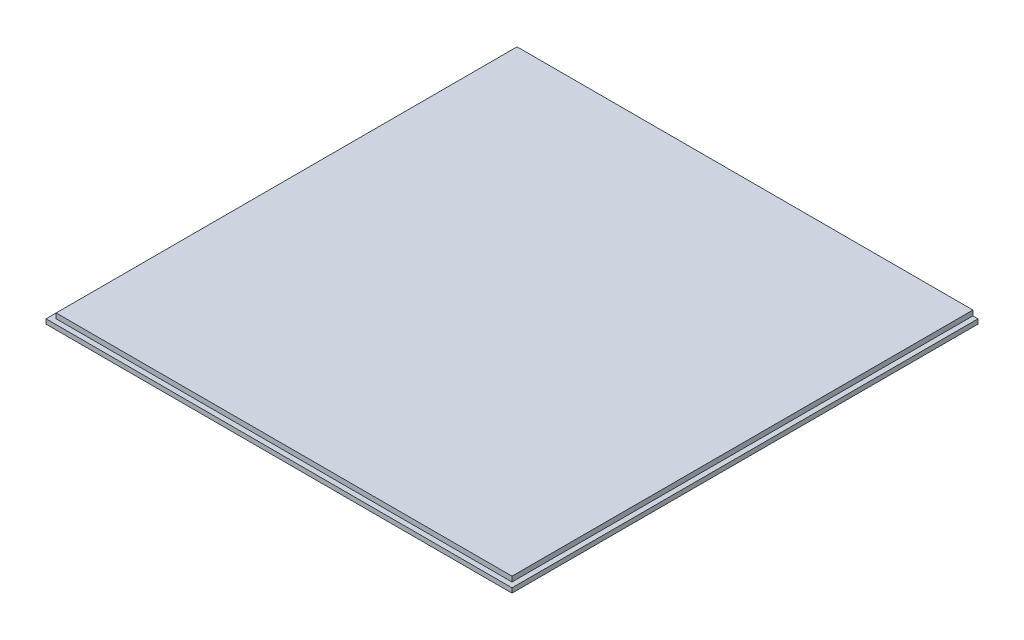
SolidWorks part; units mm, degrees
ref_plane "Front Plane" through (0, 0, 0) normal (0, 0, 1) x (1, 0, 0)
ref_plane "Top Plane" through (0, 0, 0) normal (0, 1, 0) x (1, 0, 0)
ref_plane "Right Plane" through (0, 0, 0) normal (1, 0, 0) x (0, 0, -1)
sketch "Sketch1" plane through (0, 0, 0) normal (0, 1, 0) x (1, 0, 0)
  line L1 (-438.9437, -438.9437) -> (438.9438, -438.9437)
  line L2 (-438.9437, -438.9437) -> (-438.9437, 438.9438)
  line L3 (-438.9437, 438.9438) -> (438.9438, 438.9438)
  line L4 (438.9438, -438.9437) -> (438.9438, 438.9438)
  line L5 (-438.9437, -438.9437) -> (438.9438, 438.9438) construction
  line L6 (-438.9437, 438.9438) -> (438.9438, -438.9437) construction
  point P0 (0, 0)
  dimension "D1" = 877.8875
  dimension "D2" = 877.8875
extrude "Boss-Extrude1" add sketch "Sketch1" along normal blind 18.2562 contours L2 L1 L4 L3
sketch "Sketch3" plane through (0, 18.2562, 0) normal (0, 1, 0) x (1, 0, 0)
  line L3 (429.4188, 438.9438) -> (438.9437, 438.9437)
  line L5 (438.9437, 438.9437) -> (438.9437, -438.9437)
  line L6 (429.4188, -429.4187) -> (429.4188, 438.9438)
  line L7 (-429.4187, -429.4187) -> (429.4188, -429.4187)
  line L8 (-429.4187, 438.9438) -> (-429.4187, -429.4187)
  line L9 (429.4188, -429.4187) -> (429.4188, 438.9438)
  line L10 (-429.4187, -429.4187) -> (429.4188, -429.4187)
  line L11 (-429.4187, 438.9438) -> (-429.4187, -429.4187)
  line L12 (438.9437, -438.9437) -> (-438.9437, -438.9437)
  line L13 (-438.9437, 438.9437) -> (-438.9437, -438.9437)
  line L14 (438.9437, 438.9437) -> (-438.9437, -438.9437) construction
  line L15 (438.9437, -438.9437) -> (-438.9437, 438.9437) construction
  line L16 (-429.4187, 438.9438) -> (-438.9437, 438.9437)
  point P0 (0, 0)
  dimension "D1" = 9.525
extrude "Cut-Extrude1" cut sketch "Sketch3" against normal blind 9.525
